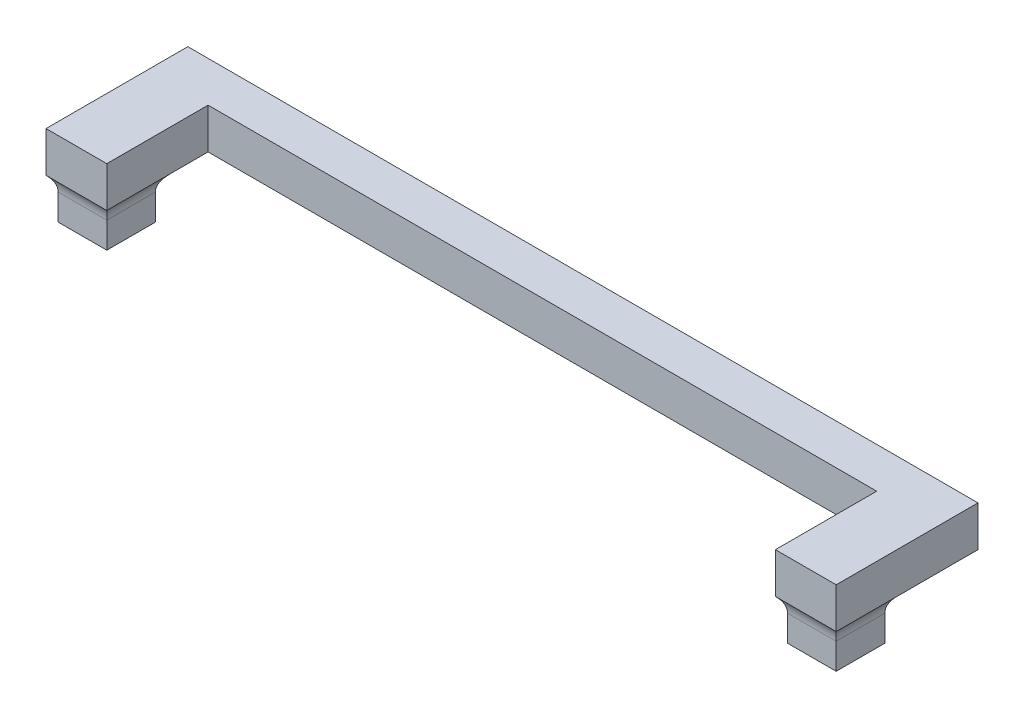
SolidWorks part; units mm, degrees
ref_plane "Front Plane" through (0, 0, 0) normal (0, 0, 1) x (1, 0, 0)
ref_plane "Top Plane" through (0, 0, 0) normal (0, 1, 0) x (1, 0, 0)
ref_plane "Right Plane" through (0, 0, 0) normal (1, 0, 0) x (0, 0, -1)
sketch "Sketch1" plane through (0, 0, 0) normal (0, 1, 0) x (1, 0, 0)
  line L1 (0, 0) -> (6.096, 0)
  line L2 (0, 0) -> (0, 6.096)
  line L3 (0, 6.096) -> (6.096, 6.096)
  line L4 (6.096, 0) -> (6.096, 6.096)
  dimension "D1" = 6.096
  dimension "D2" = 6.096
extrude "Boss-Extrude1" add sketch "Sketch1" along normal blind 5.08
sketch "Sketch2" plane through (0, 5.08, 0) normal (0, 1, 0) x (1, 0, 0)
  line L0 (0, 6.096) -> (0, 0) construction
  line L1 (-0.762, 6.858) -> (6.858, 6.858)
  line L2 (-0.762, 6.858) -> (-0.762, -0.762)
  line L3 (-0.762, -0.762) -> (6.858, -0.762)
  line L4 (6.858, 6.858) -> (6.858, -0.762)
  line L5 (0, 0) -> (6.096, 0) construction
  dimension "D1" = 7.62
  dimension "D2" = 7.62
  dimension "D3" = 0.762
  dimension "D4" = 0.762
extrude "Boss-Extrude2" add sketch "Sketch2" along normal blind 5.08
fillet "Fillet1" radius 2.54 4 edges at (3.048, 5.08, 0) (6.096, 5.08, -3.048) (3.048, 5.08, -6.096) (0, 5.08, -3.048)
sketch "Sketch3" plane through (0, 0, -6.858) normal (0, 0, -1) x (-1, 0, 0)
  line L1 (-6.858, 10.16) -> (0.762, 10.16)
  line L2 (-6.858, 10.16) -> (-6.858, 5.08)
  line L3 (-6.858, 5.08) -> (0.762, 5.08)
  line L4 (0.762, 10.16) -> (0.762, 5.08)
extrude "Boss-Extrude3" add sketch "Sketch3" along normal blind 10.16
sketch "Sketch4" plane through (-0.762, 0, 0) normal (-1, 0, 0) x (0, 0, 1)
  line L0 (-17.018, 5.08) -> (-6.858, 5.08) construction
  line L1 (-17.018, 10.16) -> (-11.938, 10.16)
  line L2 (-17.018, 10.16) -> (-17.018, 5.08)
  line L3 (-17.018, 5.08) -> (-11.938, 5.08)
  line L4 (-11.938, 10.16) -> (-11.938, 5.08)
extrude "Boss-Extrude4" add sketch "Sketch4" along normal blind 83.82
sketch "Sketch5" plane through (0, 10.16, 0) normal (0, 1, 0) x (1, 0, 0)
  line L0 (-0.762, 11.938) -> (-0.762, 17.018) construction
  line L1 (-84.582, 17.018) -> (6.858, 17.018) construction
  line L2 (-0.762, 17.018) -> (-0.762, 14.478) construction
  line L3 (-0.762, 14.478) -> (-84.582, 14.478) construction
  line L4 (-84.582, 11.938) -> (-84.582, 17.018) construction
  line L5 (-42.672, 14.478) -> (-42.672, 17.018) construction
  line L7 (-42.672, 17.018) -> (-42.672, 11.938) construction
  line L8 (-84.582, 11.938) -> (-0.762, 11.938) construction
ref_plane "Plane1" through (-42.672, 10.16, -14.478) normal (-1, 0, 0) x (0, 0, 1)
sketch "Sketch6" plane through (-84.582, 0, 0) normal (-1, 0, 0) x (0, 0, 1)
  line L1 (-17.018, 10.16) -> (-11.938, 10.16)
  line L2 (-17.018, 10.16) -> (-17.018, 5.08)
  line L3 (-17.018, 5.08) -> (-11.938, 5.08)
  line L4 (-11.938, 10.16) -> (-11.938, 5.08)
extrude "Boss-Extrude5" add sketch "Sketch6" along normal blind 7.62
sketch "Sketch7" plane through (0, 10.16, 0) normal (0, 1, 0) x (1, 0, 0)
  line L0 (-84.582, 14.478) -> (-84.582, 17.018) construction
  line L1 (-92.202, 17.018) -> (6.858, 17.018) construction
  line L2 (-84.582, 17.018) -> (-84.582, 11.938) construction
  line L3 (-92.202, 11.938) -> (-0.762, 11.938) construction
sketch "Sketch8" plane through (0, 0, -11.938) normal (0, 0, 1) x (1, 0, 0)
  line L0 (-0.762, 10.16) -> (-84.582, 10.16) construction
  line L1 (-84.582, 10.16) -> (-92.202, 10.16)
  line L2 (-84.582, 10.16) -> (-84.582, 5.08)
  line L3 (-84.582, 5.08) -> (-92.202, 5.08)
  line L4 (-92.202, 10.16) -> (-92.202, 5.08)
  line L5 (-92.202, 10.16) -> (-0.762, 10.16) construction
  dimension "D1" = 7.62
extrude "Boss-Extrude6" add sketch "Sketch8" along normal blind 12.7
sketch "Sketch9" plane through (0, 5.08, 0) normal (0, -1, 0) x (1, 0, 0)
  line L1 (-91.44, 0) -> (-85.344, 0)
  line L2 (-91.44, 0) -> (-91.44, -6.096)
  line L3 (-91.44, -6.096) -> (-85.344, -6.096)
  line L4 (-85.344, 0) -> (-85.344, -6.096)
  line L5 (-88.392, 0.762) -> (-88.392, -6.3319) construction
  line L6 (-92.202, 0.762) -> (-84.582, 0.762) construction
  line L7 (-84.582, 0.762) -> (-84.582, -11.938) construction
  dimension "D1" = 6.096
  dimension "D2" = 6.096
  dimension "D3" = 0.762
  dimension "D4" = 0.762
extrude "Boss-Extrude7" add sketch "Sketch9" along normal blind 5.08
sketch "Sketch11" plane through (0, 5.08, 0) normal (0, -1, 0) x (1, 0, 0)
  line L0 (-84.582, 0.762) -> (-84.582, -11.938) construction
  line L1 (-92.202, 0.762) -> (-84.582, 0.762)
  line L2 (-92.202, 0.762) -> (-92.202, -6.9027)
  line L3 (-92.202, -6.9027) -> (-84.582, -6.9027)
  line L4 (-84.582, 0.762) -> (-84.582, -6.9027)
fillet "Fillet7" radius 2.54 1 edges at (-85.344, 5.08, -3.048)
fillet "Fillet8" radius 2.54 1 edges at (-88.011, 5.08, 0)
fillet "Fillet9" radius 2.54 1 edges at (-91.44, 5.08, -2.667)
fillet "Fillet11" radius 1.778 1 edges at (-88.392, 5.08, -6.096)
